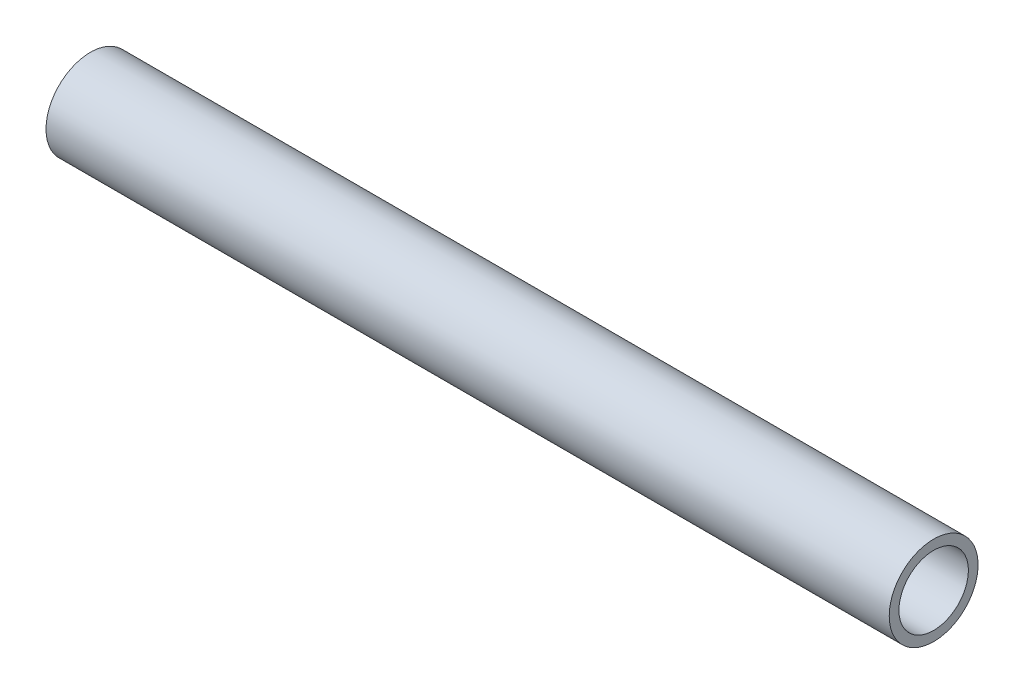
SolidWorks part; units mm, degrees
ref_plane "Front Plane" through (0, 0, 0) normal (0, 0, 1) x (1, 0, 0)
ref_plane "Top Plane" through (0, 0, 0) normal (0, 1, 0) x (1, 0, 0)
ref_plane "Right Plane" through (0, 0, 0) normal (1, 0, 0) x (0, 0, -1)
sketch "Hose_8 Sketch" plane through (0, 0, 0) normal (0, 0, 1) x (1, 0, 0)
  line L0 (-1000, 0) -> (1000, 0) construction
  line L1 (-65, 5.35) -> (-65, 6.85)
  line L2 (-65, 6.85) -> (65, 6.85)
  line L3 (65, 6.85) -> (65, 5.35)
  line L4 (65, 5.35) -> (-65, 5.35)
revolve "Hose_8" add sketch "Hose_8 Sketch" angle 360 about L0
ref_axis "Engine Axis" through (71.5, 0, 0) along (-1, 0, 0)
